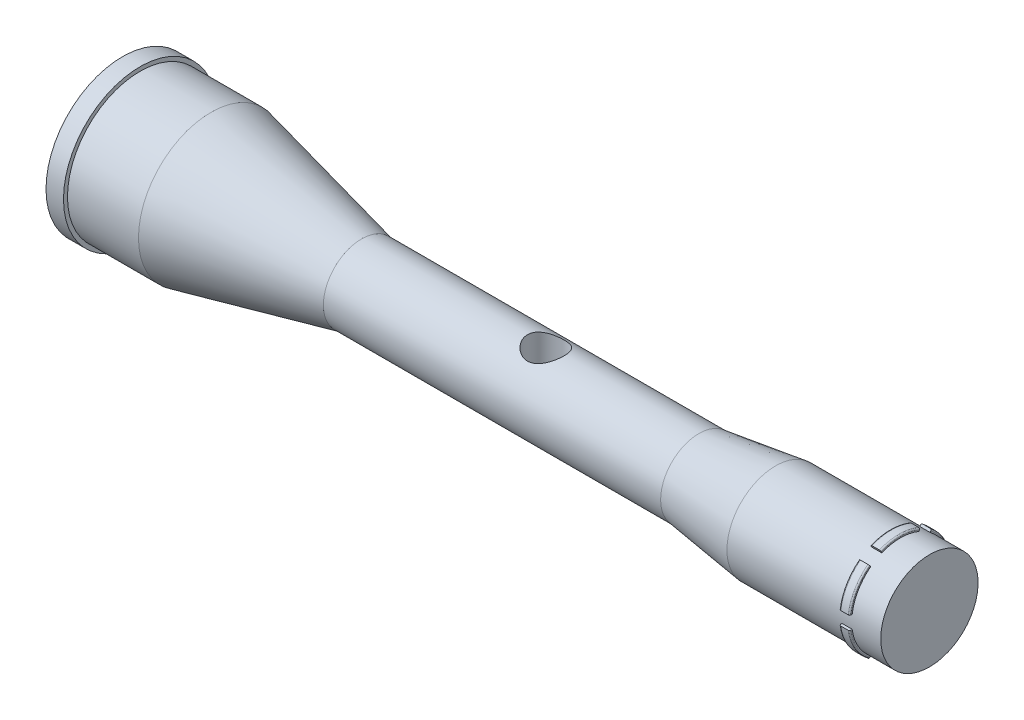
SolidWorks part; units mm, degrees
ref_plane "Front Plane" through (0, 0, 0) normal (0, 0, 1) x (1, 0, 0)
ref_plane "Top Plane" through (0, 0, 0) normal (0, 1, 0) x (1, 0, 0)
ref_plane "Right Plane" through (0, 0, 0) normal (1, 0, 0) x (0, 0, -1)
sketch "Sketch1" plane through (0, 0, 0) normal (0, 1, 0) x (1, 0, 0)
  line L0 (-147.75, 0) -> (147.75, 0) construction
  line L1 (-147.75, 0) -> (-147.75, 28.025)
  line L2 (-60.19, 14) -> (63.31, 14)
  line L3 (-147.75, 28.025) -> (-141.35, 28.025)
  line L4 (-141.35, 28.025) -> (-141.35, 26.56)
  line L5 (-141.35, 26.56) -> (-115.35, 26.56)
  line L6 (147.75, 0) -> (147.75, 17.82)
  line L7 (147.75, 17.82) -> (91.41, 17.82)
  line L8 (-60.19, 14) -> (-115.35, 26.56)
  line L9 (63.31, 14) -> (91.41, 17.82)
  line L10 (-147.75, 0) -> (147.75, 0)
  point P2 (-56.0158, 14)
  point P3 (0, 0)
  dimension "D1" = 295.5
  dimension "D2" = 28
  dimension "D3" = 123.5
  dimension "D4" = 6.4
  dimension "D5" = 28.025
  dimension "D6" = 26.56
  dimension "D7" = 26
  dimension "D8" = 35.64
  dimension "D9" = 28.1
  dimension "D10" = 55.16
revolve "Revolve1" add sketch "Sketch1" angle 360 about L0 other way angle 360
ref_plane "Plane1" through (137.11, 0, 0) normal (1, 0, 0) x (0, 0, -1)
sketch "Sketch2" plane through (137.11, 0, 0) normal (1, 0, 0) x (0, 0, -1)
  line L0 (0, 0) -> (-7.1753, 17.3227)
  line L1 (0, 0) -> (7.1753, 17.3227)
  line L2 (0, 0) -> (0, 18.75) construction
  line L3 (0, 0) -> (11.4143, 14.8754)
  line L4 (0, 0) -> (18.5896, 2.4474)
  line L5 (0, 0) -> (18.5896, -2.4474)
  line L6 (0, 0) -> (11.4143, -14.8754)
  line L7 (0, 0) -> (7.1753, -17.3227)
  line L8 (0, 0) -> (-7.1753, -17.3227)
  line L9 (0, 0) -> (-11.4143, -14.8754)
  line L10 (0, 0) -> (-18.5896, -2.4474)
  line L11 (0, 0) -> (-18.5896, 2.4474)
  line L12 (0, 0) -> (-11.4143, 14.8754)
  circle A0 centre (0, 0) radius 17.82 construction
  circle A1 centre (0, 0) radius 17.82
  circle A2 centre (0, 0) radius 18.75
  point P19 (0, 0)
  dimension "D1" = 37.5
  dimension "D2" = 45
  dimension "D3" = 22.5
  dimension "D4" = 6
extrude "Boss-Extrude1" add sketch "Sketch2" against normal blind 3.73 separate body contours L2 A1 L1 A2 | A1 L2 A2 L0 | L4 A2 L3 A1 | L6 A2 L5 A1 | L8 A2 L7 A1 | L10 A2 L9 A1 | L12 A2 L11 A1 region at (137.11, 17.8225, 3.5451) region at (137.11, 17.8225, -3.5451) region at (137.11, 8.9112, -15.4347) region at (137.11, -8.9112, -15.4347) region at (137.11, -17.8225, 0) region at (137.11, -8.9112, 15.4347) region at (137.11, 8.9112, 15.4347)
fillet "Fillet1" radius 0.5 2 edges at (133.38, 9.375, -16.238) (137.11, 9.375, -16.238)
fillet "Fillet2" radius 0.5 2 edges at (133.38, 18.75, 0) (137.11, 18.75, 0)
fillet "Fillet3" radius 0.5 2 edges at (133.38, 9.375, 16.238) (137.11, 9.375, 16.238)
fillet "Fillet4" radius 0.5 2 edges at (133.38, -9.375, 16.238) (137.11, -9.375, 16.238)
fillet "Fillet5" radius 0.5 2 edges at (137.11, -18.75, 0) (133.38, -18.75, 0)
fillet "Fillet6" radius 0.5 2 edges at (137.11, -9.375, -16.238) (133.38, -9.375, -16.238)
sketch "Sketch3" plane through (0, 0, 0) normal (0, 1, 0) x (1, 0, 0)
  line L0 (63.31, -14) -> (63.31, 14) construction
  circle A0 centre (7.27, 0) radius 6.7027
  point P2 (0, 0)
  dimension "D1" = 56.04
extrude "Cut-Extrude1" cut sketch "Sketch3" against normal through all both and the other way through all
